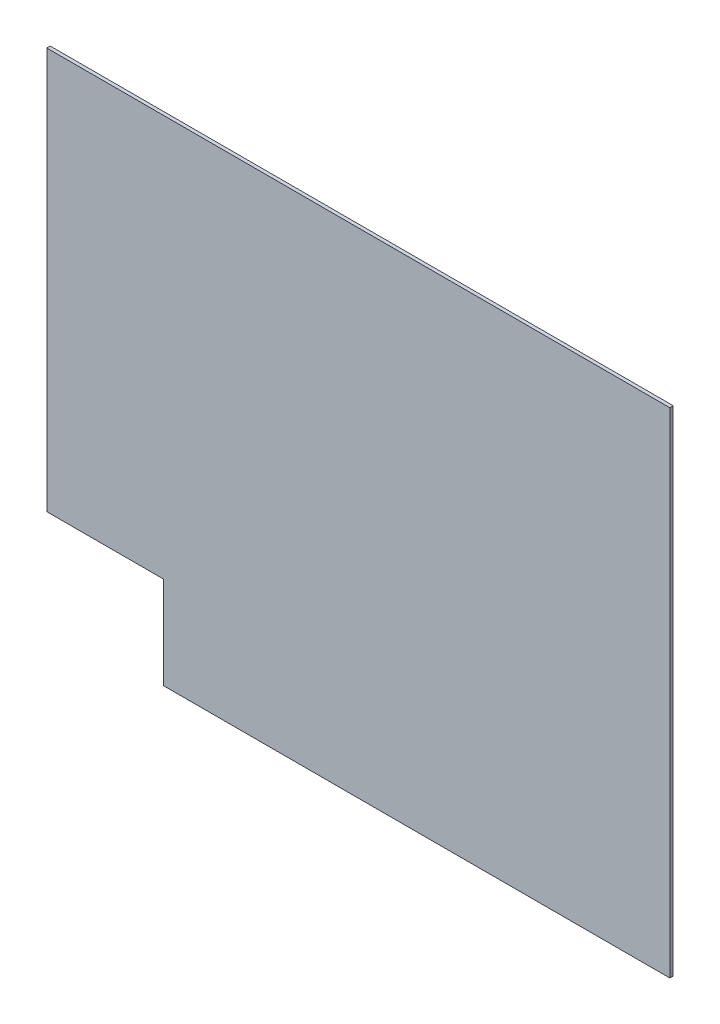
SolidWorks part; units mm, degrees
material "Acrylic (Medium-high impact)"
ref_plane "Front Plane" through (0, 0, 0) normal (0, 0, 1) x (1, 0, 0)
ref_plane "Top Plane" through (0, 0, 0) normal (0, 1, 0) x (1, 0, 0)
ref_plane "Right Plane" through (0, 0, 0) normal (1, 0, 0) x (0, 0, -1)
sketch "Sketch1" plane through (0, 0, 0) normal (0, 0, 1) x (1, 0, 0)
  line L1 (-289.5, -229.5) -> (289.5, -229.5)
  line L2 (-289.5, -229.5) -> (-289.5, 229.5)
  line L3 (-289.5, 229.5) -> (289.5, 229.5)
  line L4 (289.5, -229.5) -> (289.5, 229.5)
  line L5 (-289.5, -229.5) -> (289.5, 229.5) construction
  line L6 (-289.5, 229.5) -> (289.5, -229.5) construction
  point P0 (0, 0)
  dimension "D1" = 579
  dimension "D2" = 459
extrude "Boss-Extrude1" add sketch "Sketch1" along normal mid plane 3.175
sketch "Sketch2" plane through (0, 0, -1.5875) normal (0, 0, -1) x (-1, 0, 0)
  line L0 (284.75, -144.2) -> (181.75, -144.2) construction
  line L1 (181.75, -224.2) -> (181.75, -144.2) construction
  line L2 (284.75, -144.2) -> (181.75, -144.2) construction
  line L3 (181.75, -224.2) -> (181.75, -144.2) construction
  line L4 (289.5, -143.7) -> (181.25, -143.7)
  line L5 (181.25, -229.5) -> (181.25, -143.7)
  line L6 (289.5, -143.7) -> (289.5, -229.5)
  line L7 (289.5, 229.5) -> (289.5, -229.5) construction
  line L8 (289.5, -229.5) -> (181.25, -229.5)
  line L9 (289.5, -229.5) -> (-289.5, -229.5) construction
  line L10 (181.25, -224.2) -> (181.25, -143.7) construction
  line L11 (284.75, -143.7) -> (181.25, -143.7) construction
  dimension "D1" = 0.5
extrude "Cut-Extrude1" cut sketch "Sketch2" against normal up to surface (3.175 mm away) up to face at (0, 0, 1.5875)
